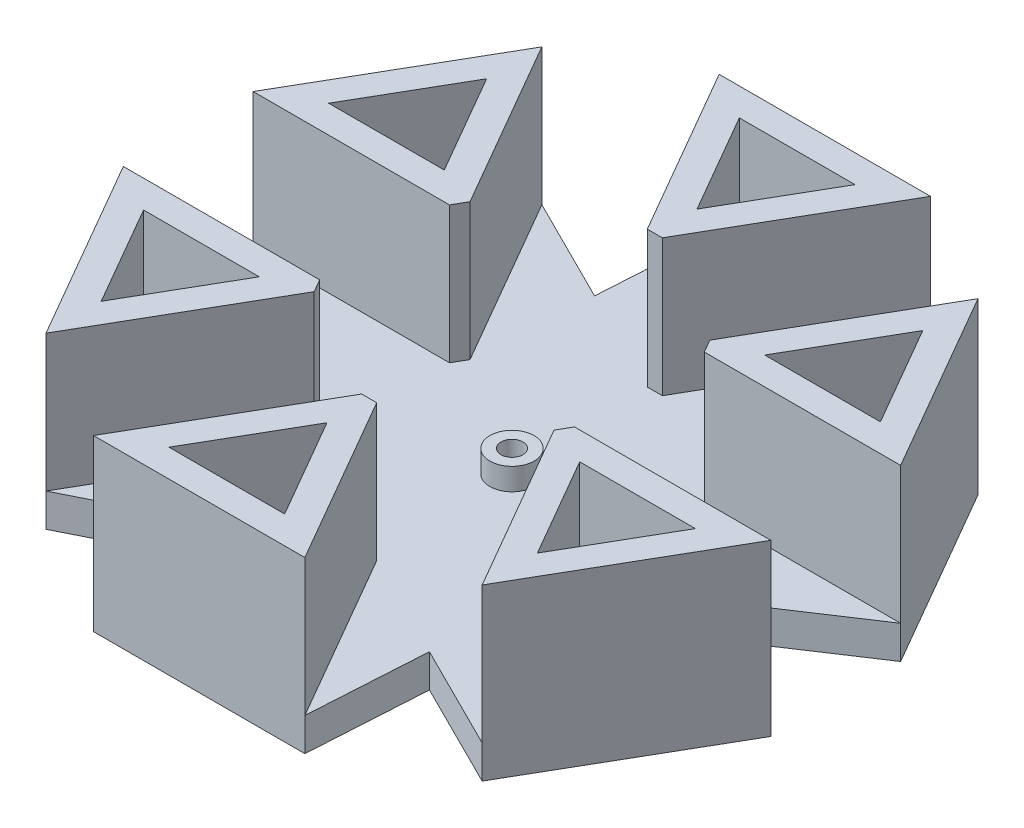
SolidWorks part; units mm, degrees
ref_plane "Front Plane" through (0, 0, 0) normal (0, 0, 1) x (1, 0, 0)
ref_plane "Top Plane" through (0, 0, 0) normal (0, 1, 0) x (1, 0, 0)
ref_plane "Right Plane" through (0, 0, 0) normal (1, 0, 0) x (0, 0, -1)
sketch "Sketch1" plane through (0, 0, 0) normal (0, 1, 0) x (1, 0, 0)
  line L26 (-128.7835, 21.2673) -> (-119.8967, 5.875)
  line L177 (-128.7835, 21.2673) -> (-109.6495, 21.2673)
  line L178 (-113.9796, 18.7673) -> (-119.2165, 9.6968)
  line L179 (-124.4534, 18.7673) -> (-119.2165, 9.6968)
  line L183 (-113.9796, 18.7673) -> (-124.4534, 18.7673)
  line L186 (-129.428, -24.7401) -> (-109.005, 10.6337) construction
  line L187 (-118.5363, 5.875) -> (-119.8967, 5.875)
  line L188 (-118.5363, 5.875) -> (-109.6495, 21.2673)
  line L189 (-129.428, 10.6337) -> (-109.005, -24.7401) construction
  line L190 (-98.7935, -7.0532) -> (-139.6395, -7.0532) construction
  line L191 (-109.6495, 21.2673) -> (-109.005, 10.6337)
  line L192 (-98.7935, -7.0532) -> (-89.9067, -1.1782)
  line L193 (-129.428, 10.6337) -> (-128.7835, 21.2673)
  line L194 (-99.4737, 15.3923) -> (-109.005, 10.6337)
  line L195 (-108.3605, 0) -> (-99.4737, 15.3923)
  line L196 (-108.3605, 0) -> (-107.6802, -1.1782)
  line L197 (-99.4737, 10.3923) -> (-94.2369, 1.3218)
  line L198 (-94.2369, 1.3218) -> (-104.7106, 1.3218)
  line L199 (-99.4737, 10.3923) -> (-104.7106, 1.3218)
  line L200 (-89.9067, -1.1782) -> (-99.4737, 15.3923)
  line L201 (-89.9067, -1.1782) -> (-107.6802, -1.1782)
  line L202 (-129.428, 10.6337) -> (-138.9593, 15.3923)
  line L203 (-148.5263, -1.1782) -> (-139.6395, -7.0532)
  line L204 (-130.7528, -1.1782) -> (-148.5263, -1.1782)
  line L205 (-130.7528, -1.1782) -> (-130.0725, 0)
  line L206 (-144.1962, 1.3218) -> (-138.9593, 10.3923)
  line L207 (-138.9593, 10.3923) -> (-133.7224, 1.3218)
  line L208 (-144.1962, 1.3218) -> (-133.7224, 1.3218)
  line L209 (-138.9593, 15.3923) -> (-148.5263, -1.1782)
  line L210 (-138.9593, 15.3923) -> (-130.0725, 0)
  line L211 (-138.9593, -29.4987) -> (-130.0725, -14.1064)
  line L212 (-138.9593, -29.4987) -> (-148.5263, -12.9282)
  line L213 (-144.1962, -15.4282) -> (-133.7224, -15.4282)
  line L214 (-138.9593, -24.4987) -> (-133.7224, -15.4282)
  line L215 (-144.1962, -15.4282) -> (-138.9593, -24.4987)
  line L216 (-130.7528, -12.9282) -> (-130.0725, -14.1064)
  line L217 (-130.7528, -12.9282) -> (-148.5263, -12.9282)
  line L218 (-148.5263, -12.9282) -> (-139.6395, -7.0532)
  line L219 (-129.428, -24.7401) -> (-138.9593, -29.4987)
  line L220 (-89.9067, -12.9282) -> (-107.6802, -12.9282)
  line L221 (-89.9067, -12.9282) -> (-99.4737, -29.4987)
  line L222 (-99.4737, -24.4987) -> (-104.7106, -15.4282)
  line L223 (-94.2369, -15.4282) -> (-104.7106, -15.4282)
  line L224 (-99.4737, -24.4987) -> (-94.2369, -15.4282)
  line L225 (-108.3605, -14.1064) -> (-107.6802, -12.9282)
  line L226 (-108.3605, -14.1064) -> (-99.4737, -29.4987)
  line L227 (-99.4737, -29.4987) -> (-109.005, -24.7401)
  line L228 (-129.428, -24.7401) -> (-128.7835, -35.3737)
  line L229 (-98.7935, -7.0532) -> (-89.9067, -12.9282)
  line L230 (-109.6495, -35.3737) -> (-109.005, -24.7401)
  line L231 (-118.5363, -19.9814) -> (-109.6495, -35.3737)
  line L232 (-118.5363, -19.9814) -> (-119.8967, -19.9814)
  line L233 (-113.9796, -32.8737) -> (-124.4534, -32.8737)
  line L234 (-124.4534, -32.8737) -> (-119.2165, -23.8032)
  line L235 (-113.9796, -32.8737) -> (-119.2165, -23.8032)
  line L236 (-128.7835, -35.3737) -> (-109.6495, -35.3737)
  line L237 (-128.7835, -35.3737) -> (-119.8967, -19.9814)
  circle A0 centre (-119.2165, -7.0532) radius 1
  circle A1 centre (-119.2165, -7.0532) radius 2
extrude "Boss-Extrude3" add sketch "Sketch1" along normal blind 15.38 contours L187 L188 L177 L26 L183 L178 L179 | L210 L209 L204 L205 L208 L206 L207 | L216 L217 L212 L211 L215 L213 L214 | L237 L236 L231 L232 L235 L233 L234 | L225 L226 L221 L220 L224 L222 L223 | L201 L200 L195 L196 L199 L197 L198 region at (-119.2165, 0, -21.0217) region at (-134.7307, 0, -7.5721) region at (-94.905, 0, -6.983) region at (-139.6395, 0, 13.1762) region at (-94.905, 0, 21.0894) region at (-124.1275, 0, 27.8003)
extrude "Boss-Extrude5" add sketch "Sketch1<7>" along normal blind 3 contours L228 L237 L232 L231 L230 L227 L226 L225 L220 L229 L192 L201 L196 L195 L194 L191 L188 L187 L26 L193 L202 L210 L205 L204 L203 L218 L217 L216 L211 L219 region at (-125.046, 0, -13.1636)
sketch "Sketch1<7>" plane through (0, 0, 0) normal (0, 1, 0) x (1, 0, 0) same geometry as "Sketch1"
extrude "Boss-Extrude6" add sketch "Sketch1<8>" along normal blind 5 contours A1 A0 region at (-121.1599, 0, 7.0532)
sketch "Sketch1<8>" plane through (0, 0, 0) normal (0, 1, 0) x (1, 0, 0) same geometry as "Sketch1"
